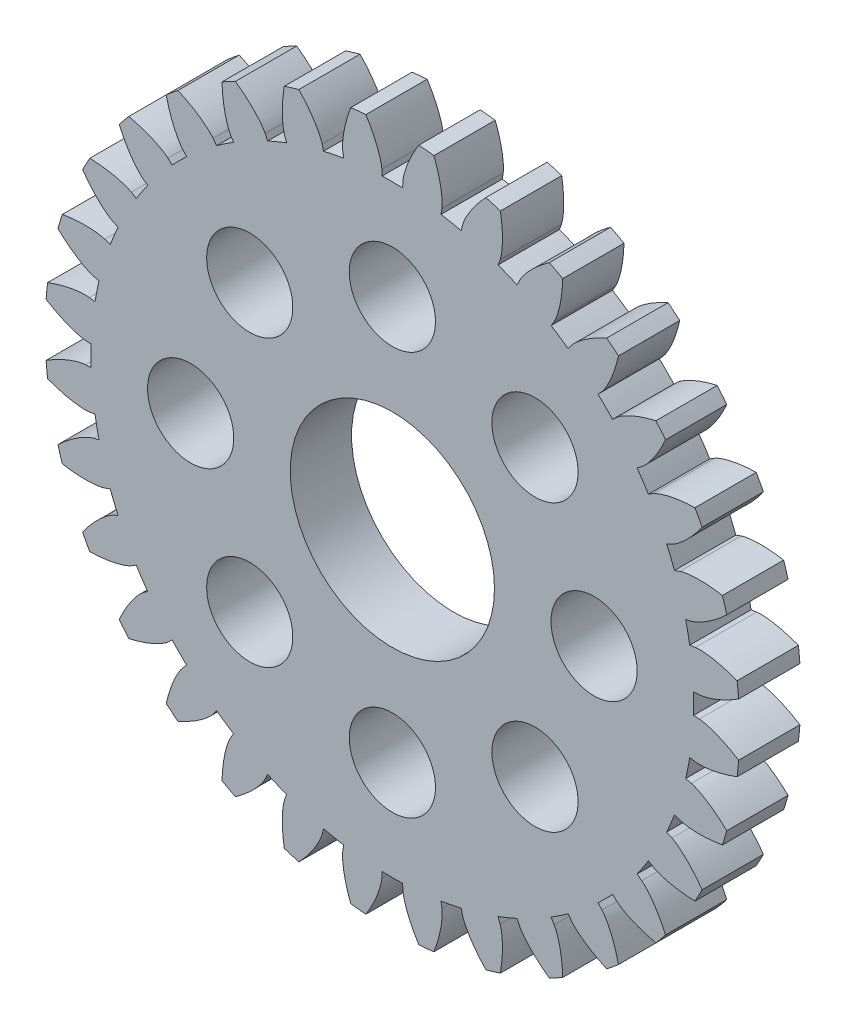
SolidWorks part; units mm, degrees
ref_plane "正面" through (0, 0, 0) normal (0, 0, 1) x (1, 0, 0)
ref_plane "平面" through (0, 0, 0) normal (0, 1, 0) x (1, 0, 0)
ref_plane "右側面" through (0, 0, 0) normal (1, 0, 0) x (0, 0, -1)
sketch "インボリュート スケッチ" plane through (0, 0, 0) normal (0, 0, 1) x (1, 0, 0)
  line L0 (-46.6927, -16.6405) -> (0.5138, -15.0263)
  line L1 (0.5138, -15.0263) -> (-0.5138, 15.0263) construction
  line L2 (0, 0) -> (0, 17) construction
  line L3 (-0.5138, 15.0263) -> (-0.5041, 14.7414)
  line L4 (0, 0) -> (0.5138, -15.0263)
  line L5 (-0.5041, 14.7414) -> (0, 14.7414)
  line L6 (0, 14.7414) -> (0, 0)
  circle A0 centre (0, 0) radius 15.0351 construction
  circle A1 centre (0, 0) radius 16 construction
  circle A2 centre (0, 0) radius 14.75 construction
  circle A3 centre (0, 0) radius 17 construction
  spline S0 degree 4 poles (-0.5138, 15.0263) (-0.5159, 15.0548) (-0.5218, 15.1117) (-0.5404, 15.2246) (-0.5892, 15.4367) (-0.6759, 15.716) (-0.8805, 16.2317) (-1.297, 17.0096) (-1.9931, 17.9739) (-3.1489, 19.1678) (-4.6974, 20.3489) (-6.5672, 21.3886) (-8.717, 22.22) (-10.9518, 22.779) (-13.2347, 23.082) (-15.65, 23.1478) (-18.6332, 22.9171) (-22.1316, 22.1876) (-26.0306, 20.7553) (-30.0637, 18.5141) (-33.7308, 15.7177) (-36.579, 12.8613) (-38.7428, 10.1707) (-40.3547, 7.7903) (-41.5274, 5.812) (-42.8455, 3.2575) (-43.965, 0.6074) (-44.8848, -2.1174) (-45.7495, -5.4571) (-46.2198, -8.0013) (-46.5006, -10.2863) (-46.6451, -12.2894) (-46.6919, -13.3002) (-46.7148, -14.1491) (-46.7213, -14.9318) (-46.7204, -15.5377) (-46.7026, -16.4013) (-46.6795, -17.0436) (-46.6261, -18.1011) (-46.5621, -18.9123) (-46.474, -19.9053) (-46.372, -20.7834) (-46.25, -21.7319) (-46.1122, -22.627) (-45.9948, -23.3298) (-45.9116, -23.7755) (-45.8682, -24.0076) knots 0 0 0 0 0 0.001401 0.002802 0.005604 0.010661 0.015718 0.02996 0.048734 0.068727 0.096889 0.125051 0.153212 0.181374 0.209535 0.237696 0.271429 0.327752 0.384075 0.440398 0.496721 0.553044 0.581206 0.609367 0.637529 0.66569 0.722013 0.750174 0.778336 0.834659 0.84874 0.86282 0.876901 0.883942 0.890982 0.900036 0.909091 0.920455 0.931818 0.943182 0.954545 0.965909 0.977273 0.988636 1 1 1 1 1 construction
  spline S1 degree 4 poles (-0.5138, 15.0263) (-0.5159, 15.0548) (-0.5218, 15.1117) (-0.5404, 15.2246) (-0.5892, 15.4367) (-0.6759, 15.716) (-0.8805, 16.2317) (-1.297, 17.0096) (-1.9931, 17.9739) (-3.1489, 19.1678) (-4.6974, 20.3489) (-6.5672, 21.3886) (-8.717, 22.22) (-10.9518, 22.779) (-13.2347, 23.082) (-15.65, 23.1478) (-18.6332, 22.9171) (-22.1316, 22.1876) (-26.0306, 20.7553) (-30.0637, 18.5141) (-33.7308, 15.7177) (-36.579, 12.8613) (-38.7428, 10.1707) (-40.3547, 7.7903) (-41.5274, 5.812) (-42.8455, 3.2575) (-43.965, 0.6074) (-44.8848, -2.1174) (-45.7495, -5.4571) (-46.2198, -8.0013) (-46.5006, -10.2863) (-46.6451, -12.2894) (-46.6919, -13.3002) (-46.7148, -14.1491) (-46.7213, -14.9318) (-46.7204, -15.5377) (-46.7081, -16.1325) (-46.6984, -16.4727) (-46.6927, -16.6405) knots 0 0 0 0 0 0.001401 0.002802 0.005604 0.010661 0.015718 0.02996 0.048734 0.068727 0.096889 0.125051 0.153212 0.181374 0.209535 0.237696 0.271429 0.327752 0.384075 0.440398 0.496721 0.553044 0.581206 0.609367 0.637529 0.66569 0.722013 0.750174 0.778336 0.834659 0.84874 0.86282 0.876901 0.883942 0.890982 0.900036 0.909091 0.909091 0.909091 0.909091 0.909091
  point P6 (-0.7851, 15.9807)
  point P12 (0, 16)
  point P24 (0, 0)
  dimension "D1" = 30.0702
  dimension "D2" = 32
  dimension "D3" = 29.5
  dimension "D4" = 34
  dimension "D5" = 0.7854
extrude "インボリュート ボス" add sketch "インボリュート スケッチ" along normal blind 3 contours S1 L0 L4 region at (-21.138, 1.3292, 0)
mirror "インボリュート ミラー" about plane through (0, 0, 3) normal (1, 0, 0) of bodies 161
sketch "歯先円 スケッチ" plane through (0, 0, 3) normal (0, 0, 1) x (1, 0, 0)
  circle A0 centre (0, 0) radius 49.5693
  circle A1 centre (0, 0) radius 17
  dimension "D1" = 34
extrude "歯先円 カット" cut sketch "歯先円 スケッチ" against normal through all
sketch "歯分割 スケッチ" plane through (0, 0, 3) normal (0, 0, 1) x (1, 0, 0)
  line L0 (-1.6663, 16.9181) -> (0, 0)
  line L1 (0, 0) -> (1.6663, 16.9181)
  line L2 (0, 0) -> (0, 16) construction
  arc A0 (-1.6663, 16.9181) -> (1.6663, 16.9181) centre (0, 0) ccw
  circle A2 centre (0, 0) radius 16 construction
  arc A3 (-1.2962, 16.9505) -> (-7.4154, -15.2974) centre (0, 0) ccw construction
  point P9 (-1.5683, 15.923)
  point P10 (1.5683, 15.923)
  dimension "D1" = 32
  dimension "D2" = 3.1416
extrude "歯分割 カット" cut sketch "歯分割 スケッチ" against normal through all
pattern_circular "歯分割 円形コピー" count 32 over 360 about axis through (0, 0, 0) along (0, 0, 1) of bodies 166
sketch "歯底円 スケッチ" plane through (0, 0, 3) normal (0, 0, 1) x (1, 0, 0)
  circle A0 centre (0, 0) radius 14.75
  dimension "D1" = 29.5
extrude "歯底円 ボス" add sketch "歯底円 スケッチ" against normal through all
sketch "軸 丸穴 スケッチ" plane through (0, 0, 3) normal (0, 0, 1) x (1, 0, 0)
  circle A0 centre (0, 0) radius 5
  dimension "D1" = 10
extrude "軸 丸穴 カット" cut sketch "軸 丸穴 スケッチ" against normal through all
sketch "軸 キー溝 スケッチ" plane through (0, 0, 3) normal (0, 0, 1) x (1, 0, 0)
  line L2 (-1.5, 3.7081) -> (-1.5, 5.4)
  line L3 (-1.5, 5.4) -> (1.5, 5.4)
  line L4 (1.5, 3.7081) -> (1.5, 5.4)
  arc A0 (-1.5, 3.7081) -> (1.5, 3.7081) centre (0, 0) ccw
  dimension "D1" = 8
  dimension "D2" = 3
  dimension "D3" = 5.4
extrude "軸 キー溝 カット" [suppressed] cut sketch "軸 キー溝 スケッチ" against normal through all
sketch "軸 Dカット スケッチ" plane through (0, 0, 3) normal (0, 0, 1) x (1, 0, 0)
  line L0 (-2.3958, 3) -> (2.3958, 3)
  arc A0 (-2.828, 2.8289) -> (2.828, 2.8289) centre (0, 0) ccw
  arc A1 (-2.3958, 3) -> (-2.828, 2.8289) centre (-2.6458, 3) ccw
  arc A2 (2.828, 2.8289) -> (2.3958, 3) centre (2.6458, 3) ccw
  dimension "D1" = 8
  dimension "D3" = 0.5
  dimension "D2" = 3
extrude "軸 Dカット カット" [suppressed] cut sketch "軸 Dカット スケッチ" against normal through all
sketch "軸 角穴 スケッチ" plane through (0, 0, 3) normal (0, 0, 1) x (1, 0, 0)
  line L0 (-5.1, 5.1) -> (5.1, 5.1)
  line L1 (-5, -5) -> (5, -5) construction
  line L2 (-5, -5) -> (-5, 5) construction
  line L3 (-5, 5) -> (5, 5) construction
  line L4 (5, -5) -> (5, 5) construction
  line L5 (-5, -5) -> (5, 5) construction
  line L6 (-5, 5) -> (5, -5) construction
  line L7 (5.1, -5.1) -> (5.1, 5.1)
  line L8 (-5.1, -5.1) -> (5.1, -5.1)
  line L9 (-5.1, -5.1) -> (-5.1, 5.1)
  point P0 (0, 0)
  dimension "D1" = 10
  dimension "D2" = 0.1
extrude "軸 角穴 カット" [suppressed] cut sketch "軸 角穴 スケッチ" against normal through all
sketch "フランジ穴 スケッチ" plane through (0, 0, 3) normal (0, 0, 1) x (1, 0, 0)
  circle A0 centre (0, 12) radius 1.6
  circle A1 centre (12, 0) radius 1.6
  circle A2 centre (0, -12) radius 1.6
  circle A3 centre (-12, 0) radius 1.6
  point P12 (0, 0)
  dimension "D2" = 3.2
  dimension "D3" = 12
  dimension "D1" = 4
extrude "フランジ穴 カット" [suppressed] cut sketch "フランジ穴 スケッチ" against normal through all
sketch "合致用スケッチ" plane through (0, 0, 3) normal (0, 0, 1) x (1, 0, 0)
  line L0 (0, 0) -> (0, 16)
  line L1 (0, 0) -> (1.5683, 15.923)
  line L2 (0, 0) -> (4.6446, 15.311)
  line L3 (0, 0) -> (7.5423, 14.1107)
  line L4 (0, 0) -> (10.1503, 12.3682)
  line L5 (0, 0) -> (12.3682, 10.1503)
  line L6 (0, 0) -> (14.1107, 7.5423)
  line L7 (0, 0) -> (15.311, 4.6446)
  line L8 (0, 0) -> (15.923, 1.5683)
  line L9 (0, 0) -> (15.923, -1.5683)
  line L10 (0, 0) -> (15.311, -4.6446)
  line L11 (0, 0) -> (14.1107, -7.5423)
  line L12 (0, 0) -> (12.3682, -10.1503)
  line L13 (0, 0) -> (10.1503, -12.3682)
  line L14 (0, 0) -> (7.5423, -14.1107)
  line L15 (0, 0) -> (4.6446, -15.311)
  line L16 (0, 0) -> (1.5683, -15.923)
  line L17 (0, 0) -> (-1.5683, -15.923)
  line L18 (0, 0) -> (-4.6446, -15.311)
  line L19 (0, 0) -> (-7.5423, -14.1107)
  line L20 (0, 0) -> (-10.1503, -12.3682)
  line L21 (0, 0) -> (-12.3682, -10.1503)
  line L22 (0, 0) -> (-14.1107, -7.5423)
  line L23 (0, 0) -> (-15.311, -4.6446)
  line L24 (0, 0) -> (-15.923, -1.5683)
  line L25 (0, 0) -> (-15.923, 1.5683)
  line L26 (0, 0) -> (-15.311, 4.6446)
  line L27 (0, 0) -> (-14.1107, 7.5423)
  line L28 (0, 0) -> (-12.3682, 10.1503)
  line L29 (0, 0) -> (-10.1503, 12.3682)
  line L30 (0, 0) -> (-7.5423, 14.1107)
  line L31 (0, 0) -> (-4.6446, 15.311)
  line L32 (0, 0) -> (-1.5683, 15.923)
  circle A2 centre (0, 0) radius 16
  point P38 (0, 0)
  dimension "D1" = 32
  dimension "D2" = 5.625
  dimension "D3" = 32
sketch "ｽｹｯﾁ2" plane through (0, 0, 0) normal (0, 0, -1) x (-1, 0, 0)
  line L0 (0, -5) -> (0, -14.75) construction
  line L1 (-3.5355, -3.5355) -> (-10.4298, -10.4298) construction
  line L2 (-5, 0) -> (-14.75, 0) construction
  line L3 (-3.5355, 3.5355) -> (-10.4298, 10.4298) construction
  line L4 (0, 5) -> (0, 14.75) construction
  line L5 (3.5355, 3.5355) -> (10.4298, 10.4298) construction
  line L6 (5, 0) -> (14.75, 0) construction
  line L7 (3.5355, -3.5355) -> (10.4298, -10.4298) construction
  circle A0 centre (0, 0) radius 5 construction
  arc A1 (-0.5041, -14.7414) -> (0.5041, -14.7414) centre (0, 0) ccw construction
  circle A2 centre (0, -9.875) radius 2.1098
  circle A3 centre (-6.9827, -6.9827) radius 2.1098
  circle A4 centre (-9.875, 0) radius 2.1098
  circle A5 centre (-6.9827, 6.9827) radius 2.1098
  circle A6 centre (0, 9.875) radius 2.1098
  circle A7 centre (6.9827, 6.9827) radius 2.1098
  circle A8 centre (9.875, 0) radius 2.1098
  circle A9 centre (6.9827, -6.9827) radius 2.1098
  point P40 (0, 0)
  dimension "D1" = 4.2195
  dimension "D2" = 8
extrude "ｶｯﾄ - 押し出し1" cut sketch "ｽｹｯﾁ2" against normal through all
equation "\"モジュール\"= 1"
equation "\"基準圧力角\"= 20"
equation "\"歯数\"= 32"
equation "\"基準円直径\"= \"歯数\" * \"モジュール\""
equation "\"基礎円直径\"= \"基準円直径\" * cos ( \"基準圧力角\" )"
equation "\"歯先円直径\"= \"基準円直径\" + 2 * \"モジュール\""
equation "\"歯底円直径\"= \"基準円直径\" - 2.5 * \"モジュール\""
equation "\"D1@インボリュート スケッチ\" = \"基礎円直径\""
equation "\"D2@インボリュート スケッチ\" = \"基準円直径\""
equation "\"D3@インボリュート スケッチ\" = \"歯底円直径\""
equation "\"D4@インボリュート スケッチ\" = \"歯先円直径\""
equation "\"D5@インボリュート スケッチ\" = Pi * \"モジュール\" / 4"
equation "\"D1@歯先円 スケッチ\" = \"歯先円直径\""
equation "\"D1@歯分割 スケッチ\" = \"基準円直径\""
equation "\"D2@歯分割 スケッチ\" = PI * \"モジュール\""
equation "\"D1@歯分割 円形コピー\" = \"歯数\""
equation "\"D1@歯底円 スケッチ\" = \"歯底円直径\""
equation "\"板厚\"= 3"
equation "\"D1@インボリュート ボス\"=\"板厚\""
equation "\"D1@合致用スケッチ\" = \"基準円直径\""
equation "\"D2@合致用スケッチ\"=180/\"歯数\""
